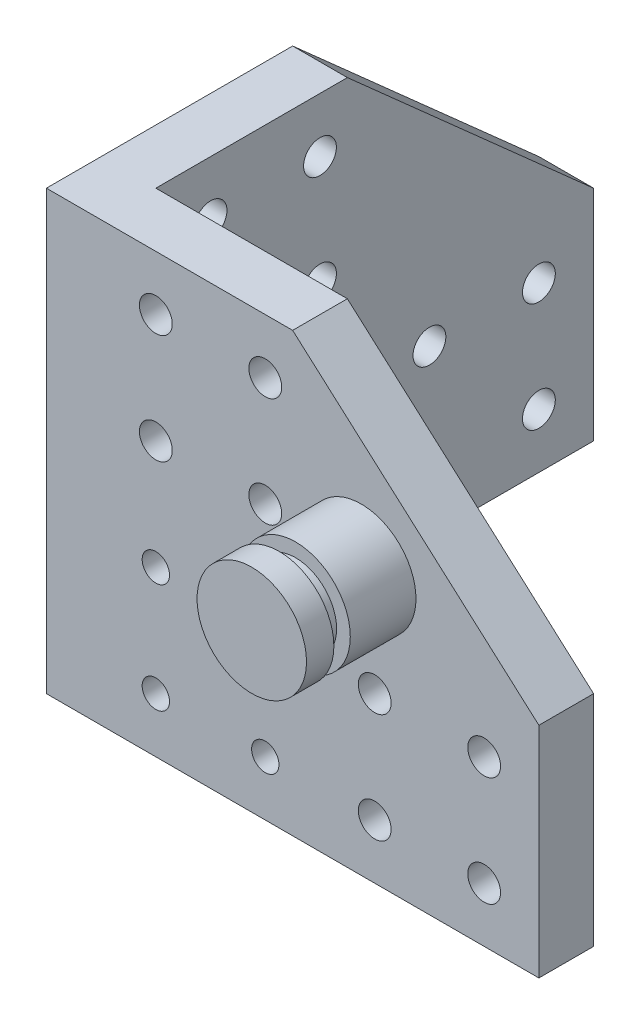
SolidWorks part; units mm, degrees
ref_plane "Front Plane" through (0, 0, 0) normal (0, 0, 1) x (1, 0, 0)
ref_plane "Top Plane" through (0, 0, 0) normal (0, 1, 0) x (1, 0, 0)
ref_plane "Right Plane" through (0, 0, 0) normal (1, 0, 0) x (0, 0, -1)
sketch "Sketch1" plane through (0, 0, 0) normal (0, 1, 0) x (1, 0, 0)
  line L0 (0, 0) -> (90, 0)
  line L1 (90, 0) -> (90, 10)
  line L2 (90, 10) -> (10, 10)
  line L3 (10, 10) -> (10, 90)
  line L4 (10, 90) -> (0, 90)
  line L5 (0, 90) -> (0, 0)
  dimension "D1" = 90
  dimension "D2" = 10
  dimension "D3" = 80
  dimension "D4" = 10
extrude "Boss-Extrude1" add sketch "Sketch1" along normal blind 80
sketch "Sketch2" plane through (0, 0, 0) normal (0, 0, 1) x (1, 0, 0)
  line L0 (90, 80) -> (90, 40)
  line L1 (90, 80) -> (90, 0) construction
  line L2 (90, 40) -> (45, 80)
  line L3 (0, 80) -> (90, 80) construction
  line L4 (45, 80) -> (90, 80)
extrude "Cut-Extrude1" cut sketch "Sketch2" against normal up to next
sketch "Sketch3" plane through (0, 0, 0) normal (-1, 0, 0) x (0, 0, 1)
  line L0 (-45, 80) -> (-90, 40)
  line L1 (-90, 80) -> (0, 80) construction
  line L2 (-90, 80) -> (-90, 0) construction
  line L3 (-90, 40) -> (-90, 80)
  line L4 (-90, 80) -> (-45, 80)
extrude "Cut-Extrude2" cut sketch "Sketch3" against normal up to next
sketch "Sketch4" plane through (0, 0, 0) normal (0, 0, 1) x (1, 0, 0)
  line L0 (0, 80) -> (0, 0) construction
  line L1 (90, 40) -> (90, 0) construction
  line L2 (0, 80) -> (45, 80) construction
  line L3 (0, 0) -> (90, 0) construction
  circle A0 centre (20, 30) radius 2.5
  circle A1 centre (40, 30) radius 2.5
  circle A2 centre (20, 10) radius 2.5
  circle A3 centre (40, 10) radius 2.5
  circle A4 centre (60, 10) radius 3
  circle A5 centre (80, 10) radius 3
  circle A6 centre (60, 30) radius 3
  circle A7 centre (80, 30) radius 3
  circle A8 centre (40, 50) radius 3
  circle A9 centre (20, 50) radius 3
  circle A10 centre (20, 70) radius 3
  circle A11 centre (40, 70) radius 3
  point P24 (0, 0)
  point P25 (0, 0)
  point P26 (0, 0)
  point P27 (0, 0)
  point P28 (0, 0)
  point P29 (0, 0)
  point P30 (0, 0)
  point P31 (0, 0)
  point P32 (0, 0)
  point P33 (0, 0)
  point P40 (80, 29.8452)
  dimension "D8" = 6
  dimension "D9" = 5
  dimension "D1" = 20
  dimension "D2" = 20
  dimension "D3" = 10
  dimension "D4" = 20
  dimension "D5" = 20
  dimension "D6" = 20
  dimension "D7" = 10
  dimension "D10" = 10
extrude "Cut-Extrude3" cut sketch "Sketch4" against normal up to next
sketch "Sketch5" plane through (0, 0, 0) normal (-1, 0, 0) x (0, 0, 1)
  line L0 (0, 80) -> (0, 0) construction
  line L1 (-90, 40) -> (-90, 0) construction
  line L2 (-90, 0) -> (0, 0) construction
  line L3 (-45, 80) -> (0, 80) construction
  circle A0 centre (-20, 70) radius 3
  circle A1 centre (-40, 70) radius 3
  circle A2 centre (-20, 50) radius 3
  circle A3 centre (-40, 50) radius 3
  circle A4 centre (-20, 30) radius 3
  circle A5 centre (-40, 30) radius 3
  circle A6 centre (-20, 10) radius 3
  circle A7 centre (-40, 10) radius 3
  circle A8 centre (-60, 10) radius 3
  circle A9 centre (-60, 30) radius 3
  circle A10 centre (-80, 30) radius 3
  circle A11 centre (-80, 10) radius 3
  point P24 (0, 0)
  point P25 (0, 0)
  point P26 (0, 0)
  point P27 (0, 0)
  point P28 (0, 0)
  point P29 (0, 0)
  dimension "D1" = 6
  dimension "D2" = 20
  dimension "D3" = 20
  dimension "D4" = 10
  dimension "D5" = 20
  dimension "D6" = 10
  dimension "D7" = 20
  dimension "D8" = 20
  dimension "D9" = 10
extrude "Cut-Extrude4" cut sketch "Sketch5" against normal up to next
sketch "Sketch6" plane through (0, 0, 0) normal (-1, 0, 0) x (0, 0, 1)
  line L0 (-90, 40) -> (-45, 80) construction
  line L1 (-67.5, 60) -> (-47.5691, 37.5777) construction
  circle A0 centre (-57.5345, 48.7889) radius 10
  point P6 (0, 0)
  dimension "D2" = 20
  dimension "D1" = 15
extrude "Boss-Extrude2" add sketch "Sketch6" along normal blind 20
sketch "Sketch7" plane through (-20, 0, 0) normal (-1, 0, 0) x (0, 0, 1)
  circle A0 centre (-57.5345, 48.7889) radius 10
  circle A1 centre (-57.5345, 48.7889) radius 7.5
  dimension "D1" = 20
  dimension "D2" = 15
extrude "Cut-Extrude5" cut sketch "Sketch7" against normal blind 3 from offset 5 offset against normal yes
sketch "Sketch8" plane through (0, 0, 0) normal (0, 0, 1) x (1, 0, 0)
  line L0 (45, 80) -> (90, 40) construction
  line L1 (67.5, 60) -> (47.5691, 37.5777) construction
  circle A0 centre (57.5345, 48.7889) radius 10
  point P6 (0, 0)
  dimension "D3" = 20
  dimension "D1" = 15
  dimension "D2" = 90
extrude "Boss-Extrude3" add sketch "Sketch8" along normal blind 20
sketch "Sketch9" plane through (0, 0, 20) normal (0, 0, 1) x (1, 0, 0)
  circle A0 centre (57.5345, 48.7889) radius 10
  circle A1 centre (57.5345, 48.7889) radius 7.5
  dimension "D1" = 20
  dimension "D2" = 15
extrude "Cut-Extrude6" cut sketch "Sketch9" against normal blind 3 from offset 5 offset against normal yes
